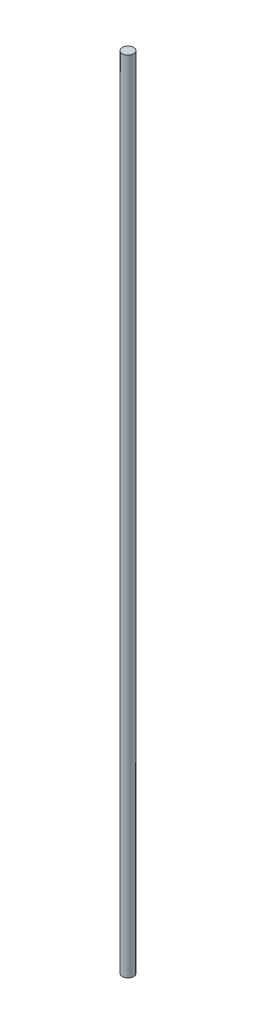
SolidWorks part; units mm, degrees
ref_plane "Płaszczyzna przednia" through (0, 0, 0) normal (0, 0, 1) x (1, 0, 0)
ref_plane "Płaszczyzna górna" through (0, 0, 0) normal (0, 1, 0) x (1, 0, 0)
ref_plane "Płaszczyzna prawa" through (0, 0, 0) normal (1, 0, 0) x (0, 0, -1)
sketch "Szkic1" plane through (0, 0, 0) normal (0, 1, 0) x (1, 0, 0)
  circle A0 centre (0, 0) radius 4
  dimension "D1" = 8
extrude "Dodanie-wyciągnięcie1" add sketch "Szkic1" along normal blind 570
